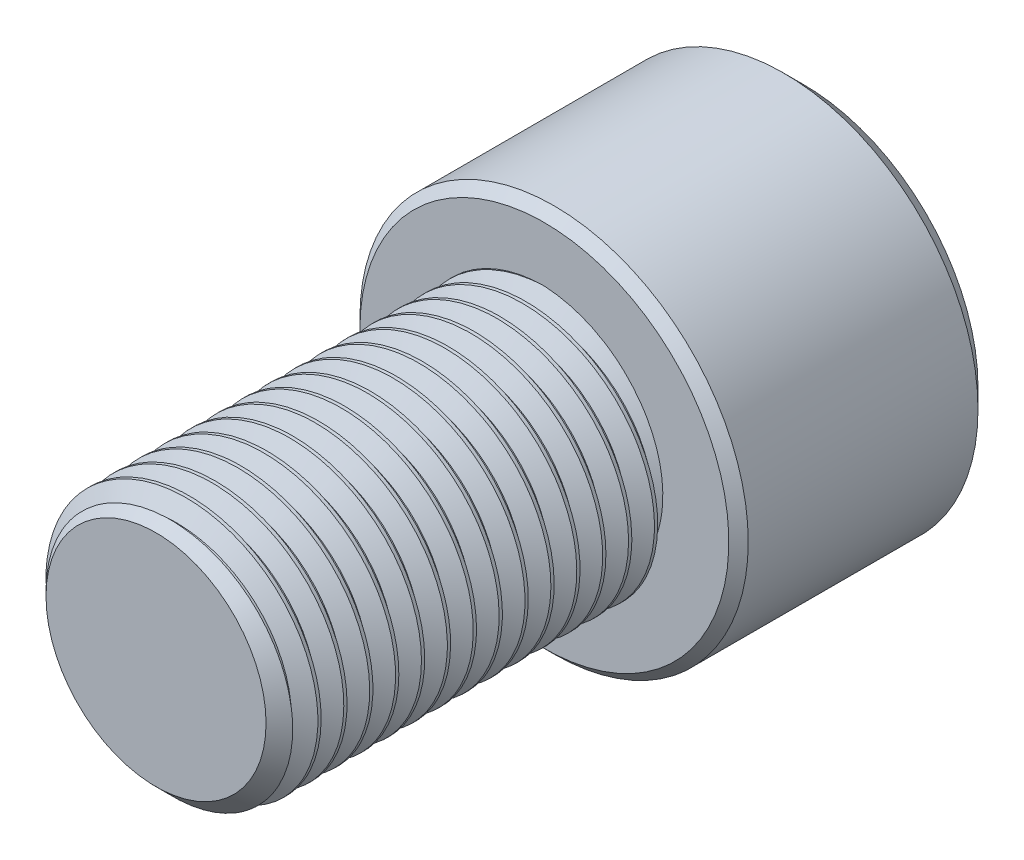
SolidWorks part; units mm, degrees
ref_plane "Front Plane" through (0, 0, 0) normal (0, 0, 1) x (1, 0, 0)
ref_plane "Top Plane" through (0, 0, 0) normal (0, 1, 0) x (1, 0, 0)
ref_plane "Right Plane" through (0, 0, 0) normal (1, 0, 0) x (0, 0, -1)
sketch "Sketch0" plane through (0, 0, 0) normal (1, 0, 0) x (0, 0, -1)
  line L0 (0, 0) -> (19.05, 0) construction
  point P2 (31.75, 0)
  point P4 (0, 0)
  dimension "D1" = 19.05
  dimension "D2" = 12.7
  dimension "Min Thread" = 0
sketch "Sketch1" plane through (0, 0, 0) normal (0, 0, 1) x (1, 0, 0)
  circle A0 centre (0, 0) radius 6.35
  dimension "OD" = 12.7
extrude "Extrude1" add sketch "Sketch1" against normal blind 19.05
sketch "Sketch2" plane through (0, 0, 0) normal (0, 0, 1) x (1, 0, 0)
  circle A0 centre (0, 0) radius 6.35 construction
  circle A1 centre (0, 0) radius 6.35
curve "Helix/Spiral1" pitch 1.27 height 20.32 turns 16 parameters "pitch"=1.27
chamfer "Chamfer3" distance 0.9525 angle 45 1 edges at (6.35, 0, 0)
sketch "Sketch3" plane through (0, 0, 0) normal (1, 0, 0) x (0, 0, -1)
  line L0 (-1.1113, 6.35) -> (-0.635, 5.5251)
  line L1 (-0.635, 5.5251) -> (-0.4763, 5.5251)
  line L2 (-0.4763, 5.5251) -> (0, 6.35)
  line L3 (-1.1113, 6.35) -> (0, 6.35)
  line L4 (-0.5556, 6.35) -> (-0.5556, 5.5251) construction
  line L5 (-0.8731, 5.9376) -> (-0.2381, 5.9376) construction
  line L6 (0, 6.35) -> (0, -6.35) construction
  dimension "D1" = 0.1588
  dimension "D2" = 0.635
  dimension "D3" = 60
sweep "Cut-Sweep1" cut profiles "Sketch3" path "Helix/Spiral1"
sketch "Sketch5" plane through (0, 0, 0) normal (1, 0, 0) x (0, 0, -1)
  line L0 (19.05, -5.5345) -> (19.05, 4.5309) construction
  line L1 (19.05, 6.35) -> (0, 6.35)
  line L2 (19.05, 6.35) -> (19.05, 0)
  line L3 (19.05, 0) -> (-2.3112, 0)
  line L4 (0, 0) -> (19.05, 0) construction
  line L5 (0, 6.35) -> (-2.3112, 0)
  line L6 (0, 0) -> (21.59, 0) construction
  dimension "D1" = 70
  dimension "D3" = 2.54
revolve "partially thread" [suppressed] add sketch "Sketch5" angle 360 about L6
sketch "Sketch6" plane through (0, 0, -19.05) normal (0, 0, -1) x (-1, 0, 0)
  circle A0 centre (0, 0) radius 9.525
  dimension "head dia" = 19.05
extrude "Extrude2" add sketch "Sketch6" along normal blind 12.7
sketch "Sketch7" plane through (0, 0, -31.75) normal (0, 0, -1) x (-1, 0, 0)
  line L1 (0, 5.4993) -> (-4.7625, 2.7496)
  line L2 (-4.7625, 2.7496) -> (-4.7625, -2.7496)
  line L3 (-4.7625, -2.7496) -> (0, -5.4993)
  line L4 (0, -5.4993) -> (4.7625, -2.7496)
  line L5 (4.7625, -2.7496) -> (4.7625, 2.7496)
  line L6 (4.7625, 2.7496) -> (0, 5.4993)
  circle A0 centre (0, 0) radius 4.7625 construction
  dimension "hex dia" = 9.525
extrude "Cut-Extrude1" cut sketch "Sketch7" against normal blind 7.1438
sketch "Sketch8" plane through (0, 0, -31.75) normal (0, 0, -1) x (-1, 0, 0)
  circle A0 centre (0, 0) radius 5.4993
extrude "Cut-Extrude2" cut sketch "Sketch8" against normal through all draft 45
chamfer "Chamfer1" distance 0.9525 angle 45 1 edges at (-9.525, 0, -31.75)
chamfer "Chamfer2" distance 0.4763 angle 45 1 edges at (-9.525, 0, -19.05)
sketch "Sketch9" plane through (0, 0, 0) normal (1, 0, 0) x (0, 0, -1)
  line L0 (0, 6.35) -> (0, -6.35) construction
  line L1 (3.175, 6.35) -> (3.175, -6.35) construction
  line L2 (31.75, 9.525) -> (31.75, -9.525) construction
  line L3 (19.05, 9.525) -> (19.05, -9.525) construction
  line L4 (19.05, 9.0488) -> (19.05, -9.0488) construction
  line L5 (31.75, -8.5725) -> (31.75, 8.5725) construction
  line L6 (19.05, -9.525) -> (19.05, 9.525) construction
  line L7 (0, 5.3975) -> (0, -5.3975) construction
  line L8 (-1.1113, 6.35) -> (0, 6.35) construction
  line L9 (3.175, 0) -> (0, 0) construction
  dimension "D1" = 3.175
equation "\"D3@Helix/Spiral1\" = \"screw length@Extrude1\"+\"pitch@Helix/Spiral1\""
equation "\"D1@Sketch3\" = \"pitch@Helix/Spiral1\"*.125"
equation "\"D2@Sketch3\" = \"pitch@Helix/Spiral1\"*.5"
equation "\"D1@Cut-Extrude1\" = \"hex dia@Sketch7\"*.75"
equation "\"D1@Chamfer1\" = \"head dia@Sketch6\"*.05"
equation "\"D1@Sketch9\" = \"pitch@Helix/Spiral1\"*2.50"
equation "\"D1@Chamfer2\" = \"D1@Chamfer1\"/2"
equation "\"D1@Chamfer3\" = \"pitch@Helix/Spiral1\"*.750"
equation "\"D1@Sketch0\" = \"screw length@Extrude1\""
equation "\"D2@Sketch0\" = \"head depth@Extrude2\""
